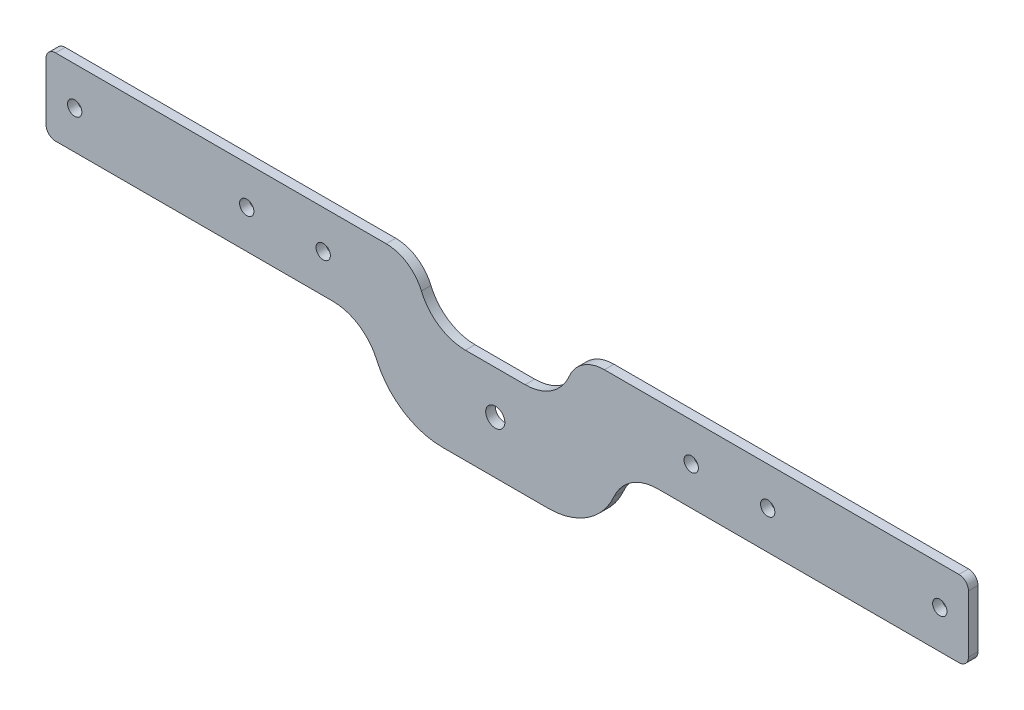
SolidWorks part; units mm, degrees
ref_plane "Спереди" through (0, 0, 0) normal (0, 0, 1) x (1, 0, 0)
ref_plane "Сверху" through (0, 0, 0) normal (0, 1, 0) x (1, 0, 0)
ref_plane "Справа" through (0, 0, 0) normal (1, 0, 0) x (0, 0, -1)
sketch "Эскиз Морковки" plane through (0, 0, 0) normal (0, 0, 1) x (1, 0, 0)
  line L0 (92, -110) -> (92, -24) construction
  line L1 (-53, -110) -> (-53, -24) construction
  line L2 (-198, -24) -> (-164, -24) construction
  line L3 (-198, -110) -> (-53, -110) construction
  line L4 (-198, -24) -> (-216, -24) construction
  line L5 (-53, -110) -> (92, -110) construction
  line L6 (-198, -110) -> (-198, -24) construction
  line L7 (58, -24) -> (92, -24) construction
  line L8 (110, -24) -> (92, -24) construction
  line L9 (-255.5, -110) -> (149.5, -110) construction
  line L10 (-198, -24) -> (-128, -24) construction
  line L11 (-128, -24) -> (-53, -24) construction
  line L12 (-128, -24) -> (0, 0) construction
  line L13 (0, 0) -> (92, -24) construction
  line L14 (-128, -24) -> (-128, -5) construction
  circle A0 centre (-198, -110) radius 57.5 construction
  circle A1 centre (-53, -110) radius 57.5 construction
  circle A2 centre (92, -110) radius 57.5 construction
  circle A3 centre (-216, -24) radius 1.5 construction
  circle A4 centre (-164, -24) radius 1.5 construction
  circle A5 centre (58, -24) radius 1.5 construction
  circle A6 centre (110, -24) radius 1.5 construction
  circle A7 centre (-87, -24) radius 1.5 construction
  circle A8 centre (-35, -24) radius 1.5 construction
  circle A9 centre (-128, -5) radius 1.5
  circle A10 centre (-128, -21) radius 1.5
  circle A11 centre (-128, -36) radius 2
  circle A12 centre (0, 40) radius 2
  circle A13 centre (-180, -24) radius 1.5
  circle A14 centre (74, -24) radius 1.5
  circle A15 centre (-71, -24) radius 1.5
  circle A16 centre (-61, -24) radius 1.5
  circle A17 centre (-45, -24) radius 1.5
  point P31 (-181, -24)
  dimension "D1" = 115
  dimension "D4" = 3
  dimension "D7" = 34
  dimension "D12" = 3
  dimension "D11" = 4
  dimension "D17" = 4
  dimension "D19" = 18
  dimension "D20" = 18
  dimension "D21" = 18
  dimension "D23" = 8
  dimension "D2" = 145
  dimension "D3" = 86
  dimension "D5" = 18
  dimension "D6" = 34
  dimension "D8" = 70
  dimension "D9" = 145
  dimension "D10" = 53
  dimension "D13" = 16
  dimension "D14" = 12
  dimension "D15" = 110
  dimension "D16" = 15
  dimension "D18" = 40
  dimension "D22" = 18
  dimension "D24" = 8
sketch "Эскиз Укропа" [suppressed] plane through (0, 0, 0) normal (0, 0, 1) x (1, 0, 0)
  line L0 (0, 0) -> (0, -24) construction
  line L1 (0, 0) -> (150, -24) construction
  line L2 (168, -24) -> (116, -24) construction
  line L3 (58, -24) -> (92, -24) construction
  line L4 (150, -110) -> (-150, -110) construction
  line L6 (150, -24) -> (150, -110) construction
  line L8 (-150, -24) -> (-150, -110) construction
  line L9 (-150, -110) -> (150, -110) construction
  line L10 (-168, -24) -> (-116, -24) construction
  line L11 (0, 0) -> (-150, -24) construction
  circle A0 centre (0, 40) radius 2
  circle A1 centre (150, -110) radius 57.5 construction
  circle A3 centre (168, -24) radius 1.5
  circle A4 centre (132, -24) radius 1.5
  circle A5 centre (116, -24) radius 1.5
  circle A6 centre (-150, -110) radius 57.5 construction
  circle A7 centre (-116, -24) radius 1.5
  circle A8 centre (-132, -24) radius 1.5
  circle A9 centre (-168, -24) radius 1.5
  circle A10 centre (0, 0) radius 3
  dimension "D1" = 4
  dimension "D2" = 40
  dimension "D3" = 24
  dimension "D4" = 3
  dimension "D5" = 150
  dimension "D10" = 115
  dimension "D11" = 6
  dimension "D6" = 86
  dimension "D7" = 18
  dimension "D8" = 18
  dimension "D9" = 34
sketch "эскиз 1" plane through (0, 0, 0) normal (0, 0, 1) x (1, 0, 0)
  line L0 (-222, -16) -> (-222, -32)
  line L1 (-222, -32) -> (-152, -32)
  line L2 (-152, -32) -> (-152, -47)
  line L3 (-222, -16) -> (-144.1949, -16)
  line L4 (-53, -110) -> (92, -110) construction
  line L5 (-29, -32) -> (-29, -16)
  line L6 (-152, -47) -> (-104, -47)
  line L9 (-134.245, -27) -> (-121.755, -27)
  line L10 (-104, -32) -> (-104, -47)
  line L11 (-53, -16) -> (-53, -110) construction
  line L12 (-104, -32) -> (-29, -32)
  line L13 (-29, -32) -> (-104, -32)
  line L14 (-138, -26) -> (-118, -26) construction
  line L15 (-111.8051, -16) -> (-29, -16)
  line L16 (-128, -24) -> (-128, -5) construction
  line L17 (-53, -110) -> (-53, -24) construction
  line L18 (-198, -16) -> (-198, -32) construction
  line L19 (-198, -110) -> (-198, -24) construction
  line L20 (-198, -24) -> (-216, -24) construction
  line L21 (-128, -27) -> (-128, -47) construction
  line L22 (-138, -27) -> (-138, -16) construction
  line L23 (-118, -26.2682) -> (-118, -16) construction
  line L24 (-144.1949, -16) -> (-144.1949, -27) construction
  line L25 (-144.1949, -27) -> (-111.8051, -27) construction
  line L26 (-111.8051, -27) -> (-111.8051, -16) construction
  circle A0 centre (-216, -24) radius 1.5
  circle A1 centre (-164, -24) radius 1.5
  circle A2 centre (-128, -36) radius 2
  circle A3 centre (-87, -24) radius 1.5
  circle A4 centre (-35, -24) radius 1.5
  circle A5 centre (-35, -24) radius 1.5 construction
  circle A6 centre (-87, -24) radius 1.5 construction
  circle A7 centre (-128, -36) radius 2 construction
  circle A8 centre (-164, -24) radius 1.5 construction
  circle A9 centre (-216, -24) radius 1.5 construction
  circle A10 centre (-128, -16) radius 10 construction
  circle A11 centre (-128, -36) radius 20 construction
  arc A12 (-121.755, -27) -> (-111.8051, -16) centre (-121.755, -17) ccw
  arc A13 (-134.245, -27) -> (-144.1949, -16) centre (-134.245, -17) cw
  circle A14 centre (-180, -24) radius 1.5
  circle A15 centre (-180, -24) radius 1.5 construction
  circle A16 centre (-71, -24) radius 1.5
  circle A17 centre (-71, -24) radius 1.5 construction
  point P25 (-128, -47)
  dimension "D6" = 9
  dimension "D5" = 20
  dimension "D1" = 24
  dimension "D2" = 24
  dimension "D3" = 16
  dimension "D4" = 11
  dimension "D7" = 70
  dimension "D8" = 8
  dimension "D9" = 5
extrude "тело маленькой арки" add sketch "эскиз 1" along normal blind 2 contours L15 L9 L3 L0 L1 L2 L6 L12 L5 region at (-125.7857, -27.471, 0)
fillet "Скругление2" radius 10 2 edges at (-104, -32, 1) (-152, -32, 1)
fillet "Скругление3" radius 15 2 edges at (-152, -47, 1) (-104, -47, 1)
fillet "Скругление16" radius 8 2 edges at (-111.8051, -16, 1) (-144.1949, -16, 1)
fillet "Скругление18" radius 2 4 edges at (-29, -16, 1) (-222, -16, 1) (-29, -32, 1) (-222, -32, 1)
sketch "Эскиз1" plane through (0, 0, 0) normal (0, 0, 1) x (1, 0, 0)
  line L0 (6, 14.0315) -> (49.0312, -16)
  line L1 (49.0312, -16) -> (116, -16)
  line L2 (116, -16) -> (116, -32)
  line L3 (116, -32) -> (44, -32)
  line L4 (44, -32) -> (8.372, -7.1351)
  line L5 (-12.7222, 2.951) -> (-10.3652, -3.6828) construction
  line L6 (-10.3652, -3.6828) -> (-19.1717, 21.1032)
  line L7 (6, 14.0315) -> (6, 46)
  line L8 (-131.0902, 0.5106) -> (-6, 41.1548)
  line L9 (-138, -16) -> (-138, -9)
  line L10 (52, -16) -> (52, -32) construction
  line L11 (-118, -11.0081) -> (-19.1717, 21.1032)
  line L12 (-8.9167, 9.5422) -> (-1.9932, 10.8179) construction
  line L13 (92, -110) -> (92, -24) construction
  line L14 (3.8054, -12.4932) -> (8.372, -7.1351)
  line L15 (-3.8054, -12.4932) -> (-8.372, -7.1351)
  line L16 (-138, -26) -> (-118, -26) construction
  line L17 (-118, -16) -> (-118, -11.0081)
  line L18 (-128, -5) -> (-128, -26) construction
  line L19 (-128, -24) -> (-128, -5) construction
  line L20 (8.9167, 9.5422) -> (1.9932, 10.8179) construction
  line L21 (-118, -26) -> (-118, -16) construction
  line L22 (6, 46) -> (-6, 46)
  line L23 (-138, 1) -> (-118, 1) construction
  line L24 (-6, 46) -> (-6, 41.1548)
  line L27 (12.7222, 2.951) -> (10.3652, -3.6828) construction
  line L31 (-138, -16) -> (-138, -26) construction
  line L32 (-12.7222, 2.951) -> (-10.3652, -3.6828) [skipped]
  circle A0 centre (-128, -21) radius 1.5
  circle A1 centre (-128, -5) radius 1.5
  circle A2 centre (-128, -5) radius 1.5 construction
  circle A3 centre (-128, -21) radius 1.5 construction
  circle A4 centre (0, 0) radius 6.5
  circle A5 centre (0, 0) radius 11 construction
  arc A6 (-8.9167, 9.5422) -> (-12.7222, 2.951) centre (-8.0107, 4.625) ccw construction
  arc A7 (1.9932, 10.8179) -> (-1.9932, 10.8179) centre (0, 0) ccw construction
  arc A8 (-3.8054, -12.4932) -> (3.8054, -12.4932) centre (0, -9.25) ccw
  arc A9 (12.7222, 2.951) -> (8.9167, 9.5422) centre (8.0107, 4.625) ccw construction
  arc A10 (8.372, -7.1351) -> (10.3652, -3.6828) centre (0, 0) ccw construction
  arc A11 (-8.372, -7.1351) -> (-10.3652, -3.6828) centre (0, 0) cw
  circle A12 centre (0, 0) radius 9.25 construction
  circle A13 centre (0, -10.45) radius 1.5
  circle A14 centre (-9.05, 5.225) radius 1.5
  circle A15 centre (9.05, 5.225) radius 1.5
  circle A16 centre (0, 0) radius 7.65 construction
  circle A17 centre (110, -24) radius 1.5
  circle A18 centre (58, -24) radius 1.5
  circle A19 centre (58, -24) radius 1.5 construction
  circle A20 centre (110, -24) radius 1.5 construction
  circle A21 centre (0, 40) radius 2
  circle A22 centre (0, 40) radius 2 construction
  arc A23 (-138, -16) -> (-118, -16) centre (-128, -16) ccw
  arc A24 (-131.0902, 0.5106) -> (-138, -9) centre (-128, -9) ccw
  circle A25 centre (52, -6.5586) radius 25.4414 construction
  circle A26 centre (74, -24) radius 1.5
  circle A27 centre (74, -24) radius 1.5 construction
  point P27 (116, -24)
  point P33 (0, 46)
  point P62 (0, 0)
  point P68 (0, 0)
  dimension "D2" = 13
  dimension "D3" = 3
  dimension "D5" = 5
  dimension "D6" = 18.5
  dimension "D7" = 22
  dimension "D14" = 3
  dimension "D17" = 15.3
  dimension "D18" = 6
  dimension "D20" = 12
  dimension "D13" = 6
  dimension "D22" = 20
  dimension "D4" = 18
  dimension "D11" = 6
  dimension "D16" = 16
  dimension "D9" = 8
  dimension "D1" = 16
  dimension "D8" = 10
  dimension "D10" = 24
  dimension "D12" = 15
  dimension "D15" = 3
  dimension "D19" = 10.45
  dimension "D21" = 5
extrude "тело большой арки" [suppressed] add sketch "Эскиз1" along normal blind 2
fillet "Скругление7" [suppressed] radius 15
fillet "Скругление8" [suppressed] radius 40
fillet "Скругление20" [suppressed] radius 6
fillet "Скругление10" [suppressed] radius 27
fillet "Скругление17" [suppressed] radius 8
fillet "Скругление21" [suppressed] radius 5
fillet "Скругление23" [suppressed] radius 2
fillet "Скругление25" [suppressed] radius 25
sketch "Эскиз6" [suppressed] plane through (0, 0, 2) normal (0, 0, 1) x (1, 0, 0)
  line L0 (-6.6599, 41.5903) -> (-133.0902, 0.5106) construction
  line L1 (5, 40) -> (5, 30.033)
  line L2 (-6.6599, 41.5903) -> (-19.6379, 37.3734)
  line L3 (-6.6599, 41.5903) -> (-133.0902, 0.5106) construction
  arc A0 (5.8569, 23.5437) -> (-19.6379, 37.3734) centre (-13.4576, 18.3523) ccw
  arc A1 (5, 30.033) -> (17.1801, 8.5703) centre (30, 30.033) ccw construction
  arc A2 (-6.6599, 41.5903) -> (-4.3406, 43.1728) centre (-8.205, 46.3455) ccw
  arc A3 (5, 30.033) -> (5.8569, 23.5437) centre (30, 30.033) ccw
  arc A4 (5, 40) -> (-0.2381, 44.9943) centre (0, 40) ccw
  arc A5 (5, 40) -> (0, 45) centre (0, 40) ccw construction
  arc A8 (-0.2381, 44.9943) -> (-4.3406, 43.1728) centre (-0.4762, 40) ccw
  arc A9 (-0.4762, 45) -> (-4.3406, 43.1728) centre (-0.4762, 40) ccw construction
  arc A10 (-6.6599, 41.5903) -> (-4.3406, 43.1728) centre (-8.205, 46.3455) ccw construction
  dimension "D1" = 20
extrude "Срез крепления тяги на внешней пластине" [suppressed] cut sketch "Эскиз6" against normal through all
sketch "Эскиз5" [suppressed] plane through (0, 0, 0) normal (0, 0, 1) x (1, 0, 0)
  line L11 (5, 15.8455) -> (51.1535, -16)
  line L14 (51.1535, -16) -> (114, -16)
  line L16 (114, -16) -> (114, -32)
  line L17 (114, -32) -> (44.4084, -32)
  line L18 (44.4084, -32) -> (8.372, -7.1351)
  line L20 (-12.7222, 2.951) -> (-20.3627, 24.4555)
  line L22 (5, 15.8455) -> (5, 50)
  line L23 (-133.4202, 1.3969) -> (-15, 44.4984)
  line L24 (-140, -16) -> (-140, -8)
  line L25 (-12.7222, 2.951) -> (-10.3652, -3.6828)
  line L26 (-120, -11.8095) -> (-20.3627, 24.4555)
  line L27 (-8.9167, 9.5422) -> (-1.9932, 10.8179) construction
  line L28 (3.8054, -12.4932) -> (8.372, -7.1351)
  line L29 (-3.8054, -12.4932) -> (-8.372, -7.1351)
  line L30 (-140, -26) -> (-120, -26) construction
  line L31 (-120, -16) -> (-120, -11.8095)
  line L32 (-130, -5) -> (-130, -26) construction
  line L33 (8.9167, 9.5422) -> (1.9932, 10.8179) construction
  line L34 (-120, -26) -> (-120, -16) construction
  line L35 (5, 50) -> (-15, 50)
  line L36 (-140, 2) -> (-120, 2) construction
  line L37 (-15, 50) -> (-15, 44.4984)
  line L38 (12.7222, 2.951) -> (10.3652, -3.6828) construction
  line L39 (-140, -16) -> (-140, -26) construction
  circle A3 centre (-130, -21) radius 1.5
  circle A4 centre (-130, -5) radius 1.5
  circle A5 centre (0, 0) radius 6.5
  circle A7 centre (0, 0) radius 11 construction
  arc A8 (-8.9167, 9.5422) -> (-12.7222, 2.951) centre (-8.0107, 4.625) ccw construction
  arc A10 (1.9932, 10.8179) -> (-1.9932, 10.8179) centre (0, 0) ccw construction
  arc A14 (-3.8054, -12.4932) -> (3.8054, -12.4932) centre (0, -9.25) ccw
  arc A20 (12.7222, 2.951) -> (8.9167, 9.5422) centre (8.0107, 4.625) ccw construction
  arc A21 (8.372, -7.1351) -> (10.3652, -3.6828) centre (0, 0) ccw construction
  arc A22 (-10.3652, -3.6828) -> (-8.372, -7.1351) centre (0, 0) ccw
  circle A23 centre (0, 0) radius 9.25 construction
  circle A24 centre (0, -10.45) radius 1.5
  circle A25 centre (-9.05, 5.225) radius 1.5
  circle A26 centre (9.05, 5.225) radius 1.5
  circle A27 centre (0, 0) radius 7.65 construction
  circle A28 centre (108, -24) radius 1.5
  circle A29 centre (56, -24) radius 1.5
  circle A30 centre (0, 40) radius 2
  arc A31 (-140, -16) -> (-120, -16) centre (-130, -16) ccw
  arc A32 (-133.4202, 1.3969) -> (-140, -8) centre (-130, -8) ccw
  point P48 (0, 0)
  point P52 (0, 0)
  dimension "D2" = 13
  dimension "D3" = 5
  dimension "D4" = 18.5
  dimension "D5" = 22
  dimension "D6" = 3
  dimension "D7" = 15.3
  dimension "D16" = 20
  dimension "D18" = 3
  dimension "D20" = 4
  dimension "D21" = 3
  dimension "D1" = 16
  dimension "D8" = 10.45
  dimension "D9" = 20
  dimension "D10" = 5
  dimension "D11" = 10
  dimension "D12" = 17
  dimension "D13" = 10
  dimension "D14" = 17
  dimension "D15" = 7
  dimension "D17" = 20
  dimension "D19" = 16
extrude "Тело внешней большой арки" [suppressed] add sketch "Эскиз5" along normal blind 2
sketch "Эскиз8" [suppressed] plane through (0, 0, 0) normal (0, 0, 1) x (1, 0, 0)
  line L0 (6, 10.8179) -> (78.1044, -16)
  line L1 (78.1044, -16) -> (174, -16)
  line L2 (174, -16) -> (174, -32)
  line L3 (174, -32) -> (75.2253, -32)
  line L4 (75.2253, -32) -> (8.372, -7.1351)
  line L5 (-12.7222, 2.951) -> (-10.3652, -3.6828) construction
  line L6 (-10.3652, -3.6828) -> (-17.9453, 17.6515)
  line L7 (6, 10.8179) -> (6, 46)
  line L10 (110, -16) -> (110, -32) construction
  line L12 (-8.9167, 9.5422) -> (-1.9932, 10.8179) construction
  line L13 (3.8054, -12.4932) -> (8.372, -7.1351)
  line L14 (-3.8054, -12.4932) -> (-8.372, -7.1351)
  line L15 (0, -10.45) -> (0, 0) construction
  line L17 (0, 0) -> (-8.0107, 4.625) construction
  line L18 (8.9167, 9.5422) -> (1.9932, 10.8179) construction
  line L19 (0, 0) -> (8.0107, 4.625) construction
  line L20 (6, 46) -> (-6, 46)
  line L22 (-6, 46) -> (-6, 37.3047)
  line L23 (12.7222, 2.951) -> (10.3652, -3.6828) construction
  circle A2 centre (0, 0) radius 6.5
  circle A3 centre (0, 0) radius 11 construction
  arc A4 (-8.9167, 9.5422) -> (-12.7222, 2.951) centre (-8.0107, 4.625) ccw construction
  arc A5 (1.9932, 10.8179) -> (-1.9932, 10.8179) centre (0, 0) ccw construction
  arc A6 (-3.8054, -12.4932) -> (3.8054, -12.4932) centre (0, -9.25) ccw
  arc A7 (12.7222, 2.951) -> (8.9167, 9.5422) centre (8.0107, 4.625) ccw construction
  arc A8 (8.372, -7.1351) -> (10.3652, -3.6828) centre (0, 0) ccw construction
  arc A9 (-8.372, -7.1351) -> (-10.3652, -3.6828) centre (0, 0) cw
  circle A10 centre (0, 0) radius 9.25 construction
  circle A11 centre (0, -10.45) radius 1.5
  circle A14 centre (0, 0) radius 7.65 construction
  circle A15 centre (168, -24) radius 1.5
  circle A16 centre (116, -24) radius 1.5
  circle A17 centre (0, 40) radius 2
  circle A21 centre (132, -24) radius 1.5
  circle A22 centre (-9.05, 5.225) radius 1.5
  circle A23 centre (9.05, 5.225) radius 1.5
  circle A24 centre (0, 40) radius 2 construction
  circle A25 centre (132, -24) radius 1.5 construction
  circle A26 centre (116, -24) radius 1.5 construction
  circle A27 centre (168, -24) radius 1.5 construction
  point P6 (174, -24)
  point P25 (0, 46)
  point P49 (0, 0)
  point P53 (0, 0)
  point P70 (0, 0)
  dimension "D2" = 13
  dimension "D3" = 5
  dimension "D4" = 18.5
  dimension "D5" = 22
  dimension "D6" = 3
  dimension "D7" = 15.3
  dimension "D1" = 16
  dimension "D8" = 10.45
  dimension "D9" = 12
  dimension "D10" = 120
  dimension "D11" = 120
  dimension "D12" = 6
  dimension "D13" = 16
  dimension "D18" = 6
  dimension "D22" = 6
  dimension "D20" = 3
